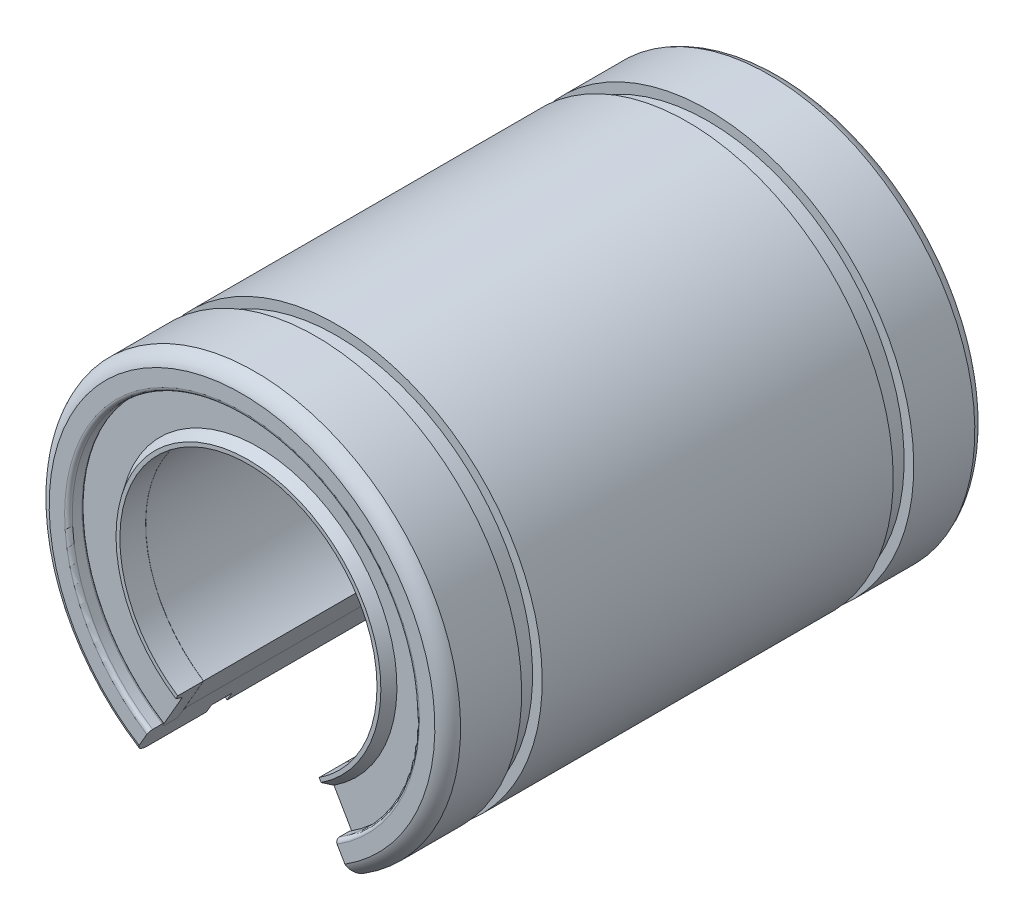
SolidWorks part; units mm, degrees
ref_plane "Спереди" through (0, 0, 0) normal (0, 0, 1) x (1, 0, 0)
ref_plane "Сверху" through (0, 0, 0) normal (0, 1, 0) x (1, 0, 0)
ref_plane "Справа" through (0, 0, 0) normal (1, 0, 0) x (0, 0, -1)
sketch "Эскиз1" plane through (0, 0, 0) normal (1, 0, 0) x (0, 0, -1)
  line L0 (-43.3432, 0) -> (33.9644, 0) construction
  line L1 (0, 10) -> (0, 0) construction
  line L2 (-21, 16) -> (21, 16)
  line L3 (-21, 16) -> (-21, 10)
  line L4 (-21, 10) -> (21, 10)
  line L5 (21, 16) -> (21, 10)
  line L6 (-13.65, 15.25) -> (13.65, 15.25) construction
  line L7 (-15.25, 16) -> (-13.65, 16)
  line L8 (-15.25, 16) -> (-15.25, 15.25)
  line L9 (-15.25, 15.25) -> (-13.65, 15.25)
  line L10 (-13.65, 16) -> (-13.65, 15.25)
  line L11 (13.65, 16) -> (15.25, 16)
  line L12 (13.65, 16) -> (13.65, 15.25)
  line L13 (13.65, 15.25) -> (15.25, 15.25)
  line L14 (15.25, 16) -> (15.25, 15.25)
  line L15 (0, 10) -> (0, 15.25) construction
  line L16 (-21, 13) -> (21, 13)
  line L17 (-19.75, 13.5) -> (-21, 13.5)
  line L18 (-19.75, 13) -> (-18.5, 13)
  line L19 (-19.75, 13) -> (-19.75, 14)
  line L20 (-19.75, 14) -> (-18.5, 14)
  line L21 (-18.5, 13) -> (-18.5, 14)
  line L22 (19.75, 13) -> (18.5, 13)
  line L23 (19.75, 13) -> (19.75, 14)
  line L24 (19.75, 14) -> (18.5, 14)
  line L25 (18.5, 13) -> (18.5, 14)
  line L26 (19.75, 13.5) -> (21, 13.5)
  line L27 (19.75, 13) -> (19.75, 10.8)
  line L28 (19.75, 10.8) -> (20.5, 10.3)
  line L29 (20.5, 10.3) -> (20.5, 10)
  line L30 (20.5, 10) -> (-20.5, 10)
  line L31 (-20.5, 10) -> (-20.5, 10.3)
  line L32 (-20.5, 10.3) -> (-19.75, 10.8)
  line L33 (-19.75, 10.8) -> (-19.75, 13)
  line L35 (18.5, 13) -> (18.49, 13)
  line L36 (18.5, 13) -> (18.5, 10)
  line L37 (18.5, 10) -> (18.49, 10)
  line L38 (18.49, 13) -> (18.49, 10)
  line L39 (-18.5, 13) -> (-18.49, 13)
  line L40 (-18.5, 13) -> (-18.5, 10)
  line L41 (-18.5, 10) -> (-18.49, 10)
  line L42 (-18.49, 13) -> (-18.49, 10)
  arc A0 (-21, 15) -> (-20, 16) centre (-19.5646, 14.5646) cw
  arc A1 (20, 16) -> (21, 15) centre (19.5646, 14.5646) cw
  arc A2 (18.2, 13) -> (18.5, 13.3) centre (18.2, 13.3) ccw
  arc A3 (18.5, 13.7) -> (18.8, 14) centre (18.8, 13.7) cw
  arc A4 (19.45, 14) -> (19.75, 13.7) centre (19.45, 13.7) cw
  arc A5 (19.75, 13.7) -> (19.95, 13.5) centre (19.95, 13.7) ccw
  arc A6 (20.7, 13.5) -> (21, 13.8) centre (20.7, 13.8) ccw
  arc A7 (-18.2, 13) -> (-18.5, 13.3) centre (-18.2, 13.3) cw
  arc A8 (-18.5, 13.7) -> (-18.8, 14) centre (-18.8, 13.7) ccw
  arc A9 (-19.45, 14) -> (-19.75, 13.7) centre (-19.45, 13.7) ccw
  arc A10 (-19.75, 13.7) -> (-19.95, 13.5) centre (-19.95, 13.7) cw
  arc A11 (-20.7, 13.5) -> (-21, 13.8) centre (-20.7, 13.8) cw
  dimension "D15" = 1.5
  dimension "D16" = 1.5
  dimension "D25" = 0.3
  dimension "D1" = 20
  dimension "D2" = 32
  dimension "D3" = 42
  dimension "D4" = 30.5
  dimension "D5" = 1.6
  dimension "D6" = 15.25
  dimension "D7" = 1.25
  dimension "D8" = 1.25
  dimension "D9" = 1
  dimension "D10" = 1
  dimension "D11" = 1.25
  dimension "D12" = 1.25
  dimension "D13" = 1
  dimension "D14" = 1
  dimension "D17" = 1
  dimension "D18" = 1
  dimension "D19" = 0.3
  dimension "D20" = 0.8
  dimension "D21" = 0.75
  dimension "D22" = 0.75
  dimension "D23" = 0.3
  dimension "D24" = 0.8
  dimension "D26" = 0.01
  dimension "D27" = 0.01
revolve "Повернуть1" add sketch "Эскиз1" angle 360 about L0 region at (0, 13.4862, 19.125) region at (0, 11.3805, 19.2185) region at (0, 11.5, 0) region at (0, 11.3805, -19.2185) region at (0, 13.4862, -19.125)
revolve "Повернуть2" add sketch "Эскиз1<3>" angle 360 about L0 region at (0, 14.5055, 0) region at (0, 13.933, 19.683) region at (0, 13.933, 18.567) region at (0, 13.933, -19.683) region at (0, 13.933, -18.567)
sketch "Эскиз1<3>" plane through (0, 0, 0) normal (1, 0, 0) x (0, 0, -1) same geometry as "Эскиз1"
sketch "Эскиз2" plane through (0, 0, 0) normal (0, 0, 1) x (1, 0, 0)
  line L0 (0, 0) -> (0, 1.1746) construction
  line L1 (0, 1.1746) -> (9.9158, -16)
  line L2 (9.9158, -16) -> (-9.9158, -16)
  line L3 (-9.9158, -16) -> (0, 1.1746)
  line L4 (-5.5, -8.3516) -> (5.5, -8.3516) construction
  circle A0 centre (0, 0) radius 16 construction
  circle A1 centre (0, 0) radius 10 construction
  dimension "D1" = 60
  dimension "D2" = 11
extrude "Вырез-Вытянуть1" cut sketch "Эскиз2" against normal through all both and the other way through all
